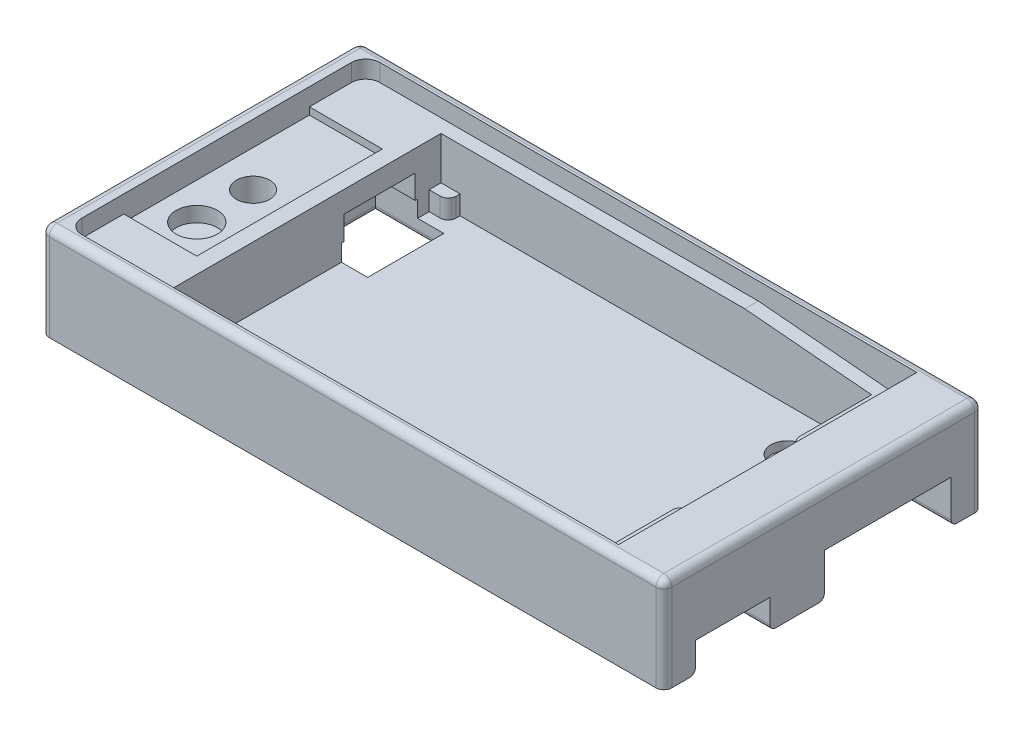
SolidWorks part; units mm, degrees
ref_plane "前视基准面" through (0, 0, 0) normal (0, 0, 1) x (1, 0, 0)
ref_plane "上视基准面" through (0, 0, 0) normal (0, 1, 0) x (1, 0, 0)
ref_plane "右视基准面" through (0, 0, 0) normal (1, 0, 0) x (0, 0, -1)
other "Configuration Table"
sketch "草图1" plane through (0, 0, 0) normal (0, 1, 0) x (1, 0, 0)
  line L0 (-39.25, 0) -> (39.25, 0) construction
  line L1 (-39.25, 20.1) -> (39.25, 20.1)
  line L2 (-39.25, 20.1) -> (-39.25, -20.1)
  line L3 (-39.25, -20.1) -> (39.25, -20.1)
  line L4 (39.25, 20.1) -> (39.25, -20.1)
  line L5 (-39.25, 20.1) -> (39.25, -20.1) construction
  line L6 (-39.25, -20.1) -> (39.25, 20.1) construction
  line L7 (-26.05, -17.1) -> (28.25, -17.1)
  line L8 (-26.05, -17.1) -> (-26.05, 17.1)
  line L9 (-26.05, 17.1) -> (28.25, 17.1)
  line L10 (28.25, -17.1) -> (28.25, 17.1)
  line L12 (32.25, 6.9973) -> (34.45, 6.9973)
  line L13 (32.25, 6.9973) -> (32.25, -6.9973)
  line L14 (32.25, -6.9973) -> (34.45, -6.9973)
  line L15 (34.45, 6.9973) -> (34.45, -6.9973)
  line L16 (-37.25, 18.8) -> (32.25, 18.8)
  line L17 (-37.25, 18.8) -> (-37.25, -18.8)
  line L18 (-37.25, -18.8) -> (32.25, -18.8)
  line L19 (32.25, 18.8) -> (32.25, -18.8)
  circle A0 centre (-32.65, 7.1) radius 2.6
  circle A1 centre (-32.65, 0) radius 2.1
  circle A2 centre (23.05, 11.6973) radius 2.1
  circle A3 centre (23.05, -11.6973) radius 2.1
  circle A4 centre (-32.65, -7.1) radius 2.6
  point P0 (0, 0)
  dimension "D1" = 4.2
  dimension "D6" = 5.2
  dimension "D2" = 5.2
  dimension "D3" = 5.4027
  dimension "D4" = 6.6
  dimension "D5" = 13
  dimension "D7" = 3
  dimension "D8" = 3
  dimension "D9" = 6.6
  dimension "D10" = 11
  dimension "D11" = 54.3
  dimension "D12" = 34.2
  dimension "D13" = 2.2
  dimension "D14" = 4.7
  dimension "D15" = 1.3
  dimension "D16" = 1.3
  dimension "D17" = 2
  dimension "D18" = 7
extrude "凸台-拉伸2" add sketch "草图1" along normal blind 2.2 contours L4 L1 L2 L3 L16 L19 L10 L12 L15 L14 L18 L17 | L15 L12 L10 L14 region at (0, 0, -19.2181) region at (33.35, 0, 0)
extrude "凸台-拉伸3" add sketch "草图1<4>" against normal blind 7.8 contours L19 L16 L17 L18 L7 L8 L9 A0 A1 A4 | L4 L1 L2 L3 L16 L19 L10 L12 L15 L14 L18 L17 | A4 | A0 | A1 | L15 L12 L13 L14 region at (0, 0, -19.2181) region at (33.35, 0, 0) region at (31.4598, 0, 0) region at (-32.65, 0, -7.1) region at (-32.65, 0, 0) region at (-32.65, 0, 7.1)
sketch "草图1<4>" plane through (0, 0, 0) normal (0, 1, 0) x (1, 0, 0) same geometry as "草图1"
sketch "草图2" plane through (0, 0, 0) normal (0, 1, 0) x (1, 0, 0)
  line L0 (-37.25, 18.8) -> (-37.25, -18.8) construction
  line L1 (-37.25, 11.7) -> (-28.05, 11.7)
  line L2 (-37.25, 11.7) -> (-37.25, -11.7)
  line L3 (-37.25, -11.7) -> (-28.05, -11.7)
  line L4 (-28.05, 11.7) -> (-28.05, -11.7)
  circle A0 centre (-32.65, 7.1) radius 2.6 construction
  circle A1 centre (-32.65, 7.1) radius 2.6 construction
  circle A2 centre (-32.65, -7.1) radius 2.6 construction
  circle A3 centre (-32.65, -7.1) radius 2.6 construction
  dimension "D1" = 4.6
  dimension "D2" = 4.6
  dimension "D3" = 4.6
extrude "切除-拉伸1" cut sketch "草图2" against normal blind 0.9
sketch "草图6" plane through (0, -0.9, 0) normal (0, 1, 0) x (1, 0, 0)
  circle A0 centre (-32.65, 7.1) radius 2.6 construction
  circle A1 centre (-32.65, 7.1) radius 2.6
  circle A2 centre (-32.65, -7.1) radius 2.6 construction
  circle A3 centre (-32.65, -7.1) radius 2.6
extrude "切除-拉伸2" cut sketch "草图6" against normal blind 1.9 contours A3 region at (-32.65, -0.9, 7.1)
sketch "草图7" plane through (0, -0.9, 0) normal (0, 1, 0) x (1, 0, 0)
  circle A0 centre (-32.65, 0) radius 2.1 construction
  circle A1 centre (-32.65, 0) radius 2.1
extrude "切除-拉伸3" cut sketch "草图7" against normal blind 1.1
sketch "草图8" plane through (0, -2, 0) normal (0, 1, 0) x (1, 0, 0)
  circle A0 centre (-32.65, 0) radius 1.2
  dimension "2.2" = 2.4
extrude "切除-拉伸4" cut sketch "草图8" against normal through all
sketch "草图9" plane through (0, -7.8, 0) normal (0, -1, 0) x (1, 0, 0)
  line L0 (39.25, -20.1) -> (39.25, 20.1) construction
  line L1 (-39.25, -20.1) -> (39.25, -20.1) construction
  line L2 (-39.25, -20.1) -> (-39.25, 20.1) construction
  line L3 (-39.25, 20.1) -> (39.25, 20.1) construction
  line L4 (39.25, -20.1) -> (39.25, 20.1)
  line L5 (-39.25, -20.1) -> (39.25, -20.1)
  line L6 (-39.25, -20.1) -> (-39.25, 20.1)
  line L7 (-39.25, 20.1) -> (39.25, 20.1)
extrude "凸台-拉伸4" add sketch "草图9" along normal blind 2
sketch "草图10" plane through (0, -7.8, 0) normal (0, 1, 0) x (1, 0, 0)
  circle A0 centre (23.05, -11.6973) radius 2.1 construction
  circle A1 centre (23.05, 11.6973) radius 2.1 construction
  circle A2 centre (23.05, -11.6973) radius 2.1
  circle A3 centre (23.05, 11.6973) radius 2.1
extrude "切除-拉伸5" cut sketch "草图10" against normal blind 1.1
sketch "草图11" plane through (0, -8.9, 0) normal (0, 1, 0) x (1, 0, 0)
  circle A0 centre (23.05, 11.6973) radius 1.2
  circle A1 centre (23.05, -11.6973) radius 1.2
  dimension "D1" = 2.4
  dimension "D2" = 2.4
extrude "切除-拉伸6" cut sketch "草图11" against normal through all
sketch "草图12" plane through (0, -9.8, 0) normal (0, -1, 0) x (1, 0, 0)
  line L0 (-26.05, -17.1) -> (28.25, -17.1) construction
  line L1 (-26.05, -17.1) -> (28.25, -17.1) construction
  line L7 (-30.8239, -4.85) -> (-26.3739, -4.85)
  line L8 (-30.8239, -4.85) -> (-30.8239, -13.85)
  line L9 (-30.8239, -13.85) -> (-26.3739, -13.85)
  line L10 (-26.3739, -4.85) -> (-26.3739, -13.85)
  line L11 (-30.8239, -4.85) -> (-26.3739, -13.85) construction
  line L12 (-30.8239, -13.85) -> (-26.3739, -4.85) construction
  line L13 (-28.5989, -9.35) -> (-23.0895, -9.35) construction
  line L14 (-31.3739, -4.55) -> (-26.3739, -4.55)
  line L15 (-31.3739, -4.55) -> (-31.3739, -14.15)
  line L16 (-31.3739, -14.15) -> (-26.3739, -14.15)
  line L17 (-26.3739, -4.55) -> (-26.3739, -14.15)
  point P6 (-28.5989, -9.35)
  dimension "D1" = 7.75
  dimension "D2" = 4.45
  dimension "D3" = 9
  dimension "D4" = 9.6
  dimension "D5" = 5
extrude "切除-拉伸7" cut sketch "草图12" against normal blind 7.1 contours L10 L7 L8 L9 region at (-28.5989, -9.8, -9.35)
extrude "切除-拉伸8" cut sketch "草图12<3>" against normal offset from surface (4.1 mm away) 3 contours L17 L14 L15 L16 L9 L8 L7 region at (-30.9321, -9.8, -9.35) up to face at (-28.5989, -2.7, -9.35)
sketch "草图12<3>" plane through (0, -9.8, 0) normal (0, -1, 0) x (1, 0, 0) same geometry as "草图12"
sketch "草图13" plane through (-26.3739, 0, 0) normal (-1, 0, 0) x (0, 0, 1)
  line L4 (-4.85, -2.7) -> (-13.85, -2.7)
  line L5 (-4.85, -2.7) -> (-13.85, -2.7)
  line L9 (-13.85, -2.7) -> (-13.85, -5.7)
  line L11 (-13.85, -5.7) -> (-14.15, -5.7)
  line L12 (-14.15, -9.8) -> (-4.55, -9.8)
  line L13 (-13.85, -5.7) -> (-14.15, -5.7)
  line L14 (-14.15, -5.7) -> (-14.15, -9.8)
  line L15 (-4.85, -5.7) -> (-4.85, -2.7)
  line L17 (-13.85, -2.7) -> (-13.85, -5.7)
  line L20 (-14.15, -9.8) -> (-4.55, -9.8)
  line L23 (-4.85, -5.7) -> (-4.85, -2.7)
  line L24 (-14.15, -5.7) -> (-14.15, -9.8)
  line L25 (-4.55, -9.8) -> (-4.55, -5.7)
  line L26 (-4.55, -9.8) -> (-4.55, -5.7)
  line L27 (-4.55, -5.7) -> (-4.85, -5.7)
  line L28 (-4.55, -5.7) -> (-4.85, -5.7)
  dimension "D1" = 0
extrude "切除-拉伸9" cut sketch "草图13" against normal up to surface (0.3239 mm away) up to face at (-26.05, -3.9, 0)
sketch "草图14" plane through (-26.05, 0, 0) normal (-1, 0, 0) x (0, 0, 1)
  line L4 (-14.15, -7.8) -> (-14.15, -9.8)
  line L5 (-14.15, -9.8) -> (-4.55, -9.8)
  line L7 (-4.55, -7.8) -> (-14.15, -7.8)
  line L9 (-14.15, -9.8) -> (-4.55, -9.8)
  line L11 (-4.55, -7.8) -> (-14.15, -7.8)
  line L12 (-14.15, -7.8) -> (-14.15, -9.8)
  line L14 (-4.55, -9.8) -> (-4.55, -7.8)
  line L15 (-4.55, -9.8) -> (-4.55, -7.8)
  dimension "D1" = 0
extrude "切除-拉伸10" cut sketch "草图14" against normal blind 3.3
fillet "圆角1" radius 1.8 4 edges at (32.25, 1.1, 18.8) (32.25, 1.1, -18.8) (-37.25, 1.1, -18.8) (-37.25, 1.1, 18.8)
fillet "圆角2" radius 1 8 edges at (39.25, -3.8, -20.1) (39.25, 2.2, 0) (39.25, -3.8, 20.1) (0, 2.2, -20.1) (-39.25, -3.8, -20.1) (0, 2.2, 20.1) (-39.25, 2.2, 0) (-39.25, -3.8, 20.1)
sketch "草图15" plane through (0, -7.8, 0) normal (0, 1, 0) x (1, 0, 0)
  line L0 (0, 0) -> (25.0264, 0) construction
  line L1 (-26.05, 17.1) -> (-23.65, 17.1)
  line L2 (-26.05, 17.1) -> (-26.05, 15.6)
  line L3 (-26.05, 15.6) -> (-23.65, 15.6)
  line L4 (-23.65, 17.1) -> (-23.65, 15.6)
  line L5 (-26.05, -15.6) -> (-23.65, -15.6)
  line L6 (-23.65, -17.1) -> (-23.65, -15.6)
  line L7 (-26.05, -17.1) -> (-23.65, -17.1)
  line L8 (-26.05, -17.1) -> (-26.05, -15.6)
  dimension "D1" = 2.4
  dimension "D2" = 1.5
extrude "凸台-拉伸5" add sketch "草图15" along normal blind 2.4
sketch "草图16" plane through (0, 0, 0) normal (0, 1, 0) x (1, 0, 0)
  line L0 (0, 0) -> (31.9375, 0) construction
  line L1 (28.25, -17.1) -> (28.25, 17.1) construction
  line L3 (30.2966, 8) -> (30.2966, -8)
  line L4 (32.25, 17) -> (32.25, -17) construction
  line L6 (30.2966, 10.6776) -> (30.2966, 8)
  line L7 (30.2966, -10.6776) -> (30.2966, -8)
  arc A0 (29.9974, 7.2957) -> (30.2966, 10.6776) centre (31.541, 8.8633) cw
  arc A1 (29.9974, -7.2957) -> (30.2966, -10.6776) centre (31.541, -8.8633) ccw
  ellipse E0 centre (28.25, 0) end of major axis (28.25, -8.1106) minor radius 4 (29.9974, -7.2957) -> (29.9974, 7.2957) ccw
  dimension "D1" = 2.2
revolve "切除-旋转1" [suppressed] cut sketch "草图16" angle 360 about L3
sketch "草图17" plane through (0, -7.8, 0) normal (0, 1, 0) x (1, 0, 0)
  circle A1 centre (-32.65, 0) radius 1.2
  circle A2 centre (-32.65, 0) radius 1.2
  dimension "D1" = 0
extrude "切除-拉伸11" cut sketch "草图17" against normal through all
sketch "草图19" plane through (0, 0, 20.1) normal (0, 0, 1) x (1, 0, 0)
  line L0 (12.25, 0) -> (34.1406, 0.2) construction
  line L1 (32.25, 2.2) -> (30.45, 2.2) construction
  line L2 (12.25, 0) -> (32.25, 2) construction
  line L6 (12.25, 0) -> (12.25, 2)
  line L11 (12.25, 0) -> (34.05, -2) construction
  line L12 (12.25, 0) -> (32.2733, -1.7518)
  line L13 (12.25, 0) -> (33.7215, -4.2678) construction
  line L14 (32.25, 2) -> (32.25, 0) construction
  line L15 (32.25, 0) -> (30.25, 0) construction
  line L17 (12.25, 2) -> (12.25, 3)
  line L18 (12.25, 3) -> (32.25, 3)
  line L19 (32.25, 2) -> (32.25, 3)
  line L20 (32.25, 2.2) -> (30.45, 2.2) construction
  line L21 (-35.45, 0) -> (30.45, 0) construction
  line L22 (-35.45, 0) -> (30.25, 0) construction
  line L23 (12.25, 2) -> (32.25, 2) construction
  line L24 (34.1416, 0) -> (32.3498, 0) construction
  line L25 (30.25, 0) -> (34.05, 0) construction
  line L26 (30.25, 0) -> (30.25, -2) construction
  line L27 (30.25, -2) -> (34.05, -2) construction
  line L28 (34.05, 0) -> (34.05, -2) construction
  line L29 (33.7215, -4.2678) -> (25.7215, -2.6777)
  line L30 (25.7215, -2.6777) -> (25.8517, -1.19)
  line L31 (34.1406, 0.2) -> (32.3489, 0.1836)
  circle A0 centre (12.25, 0) radius 20.0998 construction
  arc A3 (32.25, 2) -> (32.2733, -1.7518) centre (12.25, 0) cw
  circle A4 centre (12.25, 0) radius 21.8916 construction
  arc A5 (33.7215, -4.2678) -> (34.1406, 0.2) centre (12.25, 0) ccw
  point P17 (0, 0)
  line M8 (38.25, 1.2) -> (-38.25, 1.2)
  dimension "D1" = 2
  dimension "D2" = 20
  dimension "D3" = 5
  dimension "D4" = 2
  dimension "D5" = 20
  dimension "D6" = 6
  dimension "D7" = 1
  dimension "D8" = 1.8
  dimension "D9" = 2
  dimension "D10" = 8
  dimension "D11" = 0.2
extrude "切除-拉伸12" cut sketch "草图19" against normal up to surface (38.9 mm away) from surface contours L6 L12 M8 | L6 M8 region at (23.7042, 0.0997, 20.1) region at (22.2577, 2.0995, 20.1) up to face at (-2.5, 1.1, -18.8) starting at face at (-2.5, 1.1, 18.8)
extrude "切除-拉伸13" cut sketch "草图19<3>" against normal up to vertex (27.0973 mm away) from vertex contours L27 L12 L13 region at (30.7321, -2.2329, 20.1) up to point (34.45, 0, -6.9973) starting at point (34.45, 0, 6.9973)
sketch "草图19<3>" plane through (0, 0, 20.1) normal (0, 0, 1) x (1, 0, 0) same geometry as "草图19"
sketch "草图20" plane through (0.3556, 2.3642, 0) normal (0.195, 0.9808, 0) x (0.9808, -0.195, 0)
  line L0 (0.1121, 0) -> (28.44, 0) construction
  line L1 (28.44, 6.9973) -> (28.44, -6.9973) construction
  line L2 (28.44, 6.9973) -> (28.44, -6.9973) construction
  line L3 (28.44, 5.3609) -> (28.44, -5.3609)
  line L4 (28.44, 0) -> (31.3144, 0) construction
  line L5 (31.3144, 18.8) -> (31.3144, -18.8) construction
  line L6 (29.3869, 4.2263) -> (28.44, 5.3609) construction
  line L9 (28.44, -5.3609) -> (28.44, 5.3609) construction
  ellipse E0 centre (28.44, 0) end of major axis (28.44, 5.3609) minor radius 2.8744 (28.44, 5.3609) -> (28.44, -5.3609) cw
revolve "切除-旋转2" [suppressed] cut sketch "草图20" angle 360 about L3
fillet "圆角4" [suppressed] radius 1
fillet "圆角5" radius 1 2 edges at (-23.65, -6.6, 15.6) (-23.65, -6.6, -15.6)
sketch "草图21" plane through (0, -2, 0) normal (0, 1, 0) x (1, 0, 0)
  circle A1 centre (-32.65, 0) radius 2.1
  circle A2 centre (-32.65, 0) radius 2.1
  dimension "D1" = 0
extrude "切除-拉伸14" cut sketch "草图21" against normal up to surface (6.9 mm away) up to face at (23.05, -8.9, -10.4973)
sketch "草图22" plane through (0, -9.8, 0) normal (0, -1, 0) x (1, 0, 0)
  line L0 (0, 0) -> (39.25, 0) construction
  line L2 (-39.25, 14.6675) -> (-39.25, 5.2675)
  line L3 (31.35, 16.1208) -> (39.25, 16.1208)
  line L4 (31.35, 16.1208) -> (31.35, 6.7208)
  line L5 (31.35, 6.7208) -> (39.25, 6.7208)
  line L6 (39.25, 16.1208) -> (39.25, 6.7208)
  line L7 (31.35, 16.1208) -> (39.25, 6.7208) construction
  line L8 (31.35, 6.7208) -> (39.25, 16.1208) construction
  line L9 (-39.25, 14.6675) -> (-31.35, 14.6675)
  line L10 (-39.25, 5.2675) -> (-31.35, 5.2675)
  line L11 (-31.35, 14.6675) -> (-31.35, 5.2675)
  line L13 (39.25, -19.1) -> (39.25, 19.1) construction
  line L14 (-39.25, 19.1) -> (-39.25, -19.1) construction
  point P5 (35.3, 11.4208)
  dimension "D1" = 7.9
  dimension "D2" = 9.4
extrude "切除-拉伸15" cut sketch "草图22" against normal blind 3.7
sketch "草图23" plane through (0, -9.8, 0) normal (0, -1, 0) x (1, 0, 0)
  line L1 (39.25, -16.1357) -> (30.85, -16.1357)
  line L2 (39.25, -16.1357) -> (39.25, -0.1357)
  line L3 (39.25, -0.1357) -> (30.85, -0.1357)
  line L4 (30.85, -16.1357) -> (30.85, -0.1357)
  line L6 (32.2733, -18.8) -> (12.25, -18.8) construction
  line L7 (32.2733, -18.8) -> (12.25, -18.8) construction
  line L8 (39.25, -19.1) -> (39.25, 6.7208) construction
  line L9 (39.25, -19.1) -> (39.25, 6.7208) construction
  dimension "D1" = 8.4
  dimension "D2" = 16
extrude "切除-拉伸16" cut sketch "草图23" against normal blind 5.4
fillet "圆角6" radius 0.7 13 edges at (-35.3, -9.8, 5.2675) (35.05, -9.8, -16.1357) (30.85, -9.8, -8.1357) (35.05, -9.8, -0.1357) (35.3, -9.8, 6.7208) (35.3, -9.8, 16.1208) (31.35, -9.8, 11.4208) (-22.75, -9.8, -9.35) (-27.0619, -9.8, -14.15) (-31.3739, -9.8, -9.35) (-27.0619, -9.8, -4.55) (-31.35, -9.8, 9.9675) (-35.3, -9.8, 14.6675)
fillet "圆角7" radius 1 3 edges at (28.25, -2.29, 6.9973) (28.25, -2.29, -6.9973) (28.25, -3.1802, 0)
